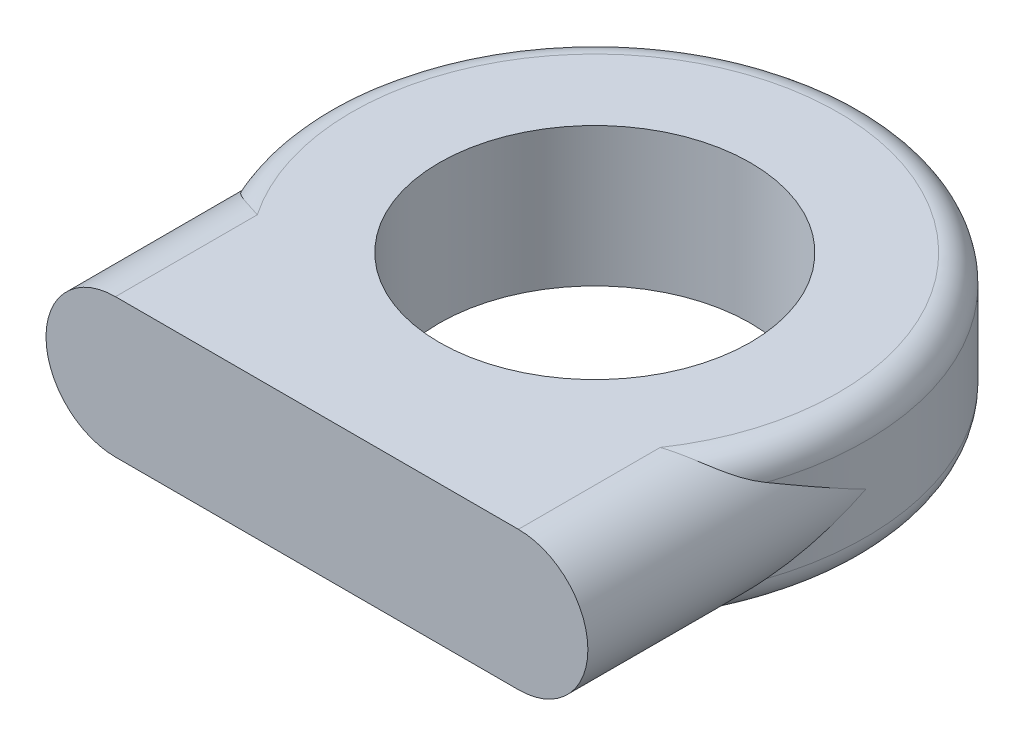
SolidWorks part; units mm, degrees
ref_plane "前视基准面" through (0, 0, 0) normal (0, 0, 1) x (1, 0, 0)
ref_plane "上视基准面" through (0, 0, 0) normal (0, 1, 0) x (1, 0, 0)
ref_plane "右视基准面" through (0, 0, 0) normal (1, 0, 0) x (0, 0, -1)
other "Configuration Table"
sketch "草图1" plane through (0, 0, 0) normal (0, 0, 1) x (1, 0, 0)
  line L0 (-7.25, 0) -> (7.25, 0) construction
  line L1 (-7.25, 2.5) -> (7.25, 2.5)
  line L2 (-7.25, -2.5) -> (7.25, -2.5)
  arc A0 (-7.25, 2.5) -> (-7.25, -2.5) centre (-7.25, 0) ccw
  arc A1 (7.25, -2.5) -> (7.25, 2.5) centre (7.25, 0) ccw
  point P2 (0, 0)
  dimension "D1" = 5
  dimension "D2" = 14.5
extrude "凸台-拉伸1" add sketch "草图1" along normal blind 10 contours A1 L1 A0 L2
sketch "草图2" plane through (0, 2.5, 0) normal (0, 1, 0) x (1, 0, 0)
  circle A0 centre (0, 0) radius 9.75
extrude "凸台-拉伸2" add sketch "草图2" against normal blind 5
fillet "圆角2" radius 1 2 edges at (0, 2.5, -9.75) (0, -2.5, -9.75)
sketch "草图3" plane through (0, 2.5, 0) normal (0, 1, 0) x (1, 0, 0)
  circle A0 centre (0, 0) radius 5.6
  dimension "D1" = 11.2
extrude "切除-拉伸1" cut sketch "草图3" against normal blind 5 contours A0
equation "\"2、15\"=10.5109"
